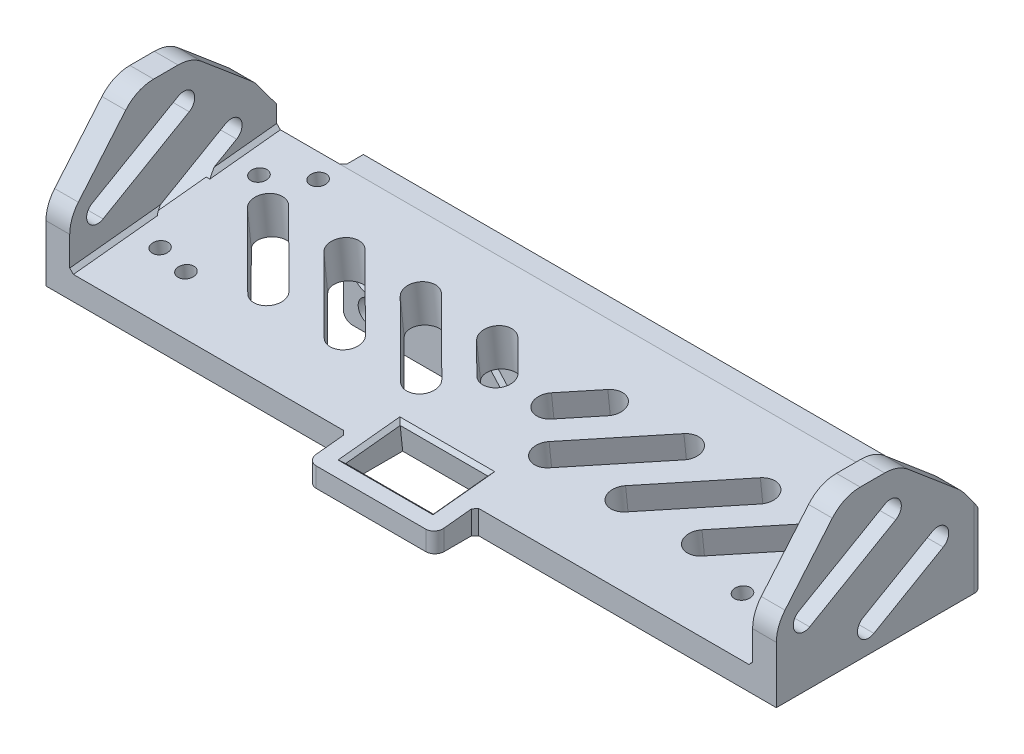
SolidWorks part; units mm, degrees
material "PPS"
ref_plane "前视基准面" through (0, 0, 0) normal (0, 0, 1) x (1, 0, 0)
ref_plane "上视基准面" through (0, 0, 0) normal (0, 1, 0) x (1, 0, 0)
ref_plane "右视基准面" through (0, 0, 0) normal (1, 0, 0) x (0, 0, -1)
sketch "ref" plane through (0, 0, 0) normal (0, 0, 1) x (1, 0, 0)
  line L257 (0, -1000) -> (0, 49000) construction
  line L346 (0, 0) -> (635.1265, 0) construction
  line L351 (-46.1708, 93.9243) -> (-46.1708, 145) construction
  line L358 (-27.9426, 92.9426) -> (-32.5, 97.5) construction
  line L394 (-24.4478, 142.8678) -> (-29.0158, 138.8343)
  line L411 (-32.3253, 137.5823) -> (-39.0335, 137.5823)
  line L414 (-42.3429, 136.3303) -> (-44.4803, 134.4431)
  line L445 (-46.1708, 130.695) -> (-46.1708, 101.1668)
  line L472 (42.3429, 136.3303) -> (44.4803, 134.4431)
  line L494 (46.1729, 155.4291) -> (33.7932, 145.5483) construction
  line L496 (32.4724, 137.5823) -> (39.0335, 137.5823)
  line L497 (25.2455, 142.6568) -> (28.9763, 139.0078)
  line L498 (27.9426, 92.9426) -> (32.5, 97.5) construction
  line L501 (-46.2756, 154.6927) -> (-33.8959, 144.8119) construction
  line L595 (-39.3354, 129.0823) -> (-39.3354, 104.0823) construction
  line L626 (-31.6538, 83.28) -> (-46.1708, 93.9243) construction
  line L628 (-39.3354, 116.5823) -> (0, 116.5823) construction
  line L629 (-15.0322, 144.0823) -> (-9.5322, 138.5823)
  line L630 (-9.5322, 138.5823) -> (9.5322, 138.5823)
  line L631 (15.0322, 144.0823) -> (9.5322, 138.5823)
  line L633 (-21.7494, 144.0823) -> (-15.0322, 144.0823)
  line L635 (15.0322, 144.0823) -> (21.7494, 144.0823)
  line L641 (-9.5322, 83.7633) -> (9.5322, 83.7633)
  line L643 (-9.5322, 83.7633) -> (-14.5322, 78.7633)
  line L644 (30.4418, 78.7633) -> (14.5322, 78.7633) construction
  line L645 (9.5322, 83.7633) -> (14.5322, 78.7633)
  line L646 (7.1054, 96.1323) -> (-7.1054, 96.1323)
  line L647 (-7.1054, 96.1323) -> (-9.7615, 92.339)
  line L648 (-9.7615, 92.339) -> (-9.7615, 90.339)
  line L649 (-9.7615, 90.339) -> (9.7615, 90.339)
  line L652 (9.7615, 92.339) -> (9.7615, 90.339)
  line L653 (7.1054, 96.1323) -> (9.7615, 92.339)
  line L666 (-35.6, 116.5823) -> (-35.6, 112.0823)
  line L668 (-32.5, 116.5823) -> (-32.5, 112.0823)
  line L670 (35.6, 116.5823) -> (35.6, 112.0823)
  line L671 (32.5, 116.5823) -> (32.5, 112.0823)
  line L681 (-19.6882, 78.7633) -> (-14.5322, 78.7633)
  line L686 (14.5322, 78.7633) -> (19.6882, 78.7633)
  line L687 (-42.4964, 96.1323) -> (-35.6, 93.9243)
  line L688 (-35.6, 93.9243) -> (-30.0524, 90.888)
  line L691 (-30.0524, 90.888) -> (-30.0524, 87.8422)
  line L692 (-30.0524, 87.8422) -> (-19.6882, 78.7633)
  line L693 (30.0524, 87.8422) -> (19.6882, 78.7633)
  line L694 (30.0524, 90.888) -> (30.0524, 87.8422)
  line L695 (35.6, 93.9243) -> (30.0524, 90.888)
  line L696 (42.4964, 96.1323) -> (35.6, 93.9243)
  line L697 (46.1708, 130.695) -> (46.1708, 101.1668)
  line L700 (-17.1276, 113.853) -> (-11.5061, 107.6186)
  line L701 (-11.5061, 107.6186) -> (11.5061, 107.6186)
  line L706 (17.1276, 113.853) -> (11.5061, 107.6186)
  line L709 (-7.1054, 129.7982) -> (7.1054, 129.7982)
  line L710 (7.1054, 129.7982) -> (9.7615, 133.5915)
  line L711 (9.7615, 133.5915) -> (9.7615, 135.5915)
  line L712 (9.7615, 135.5915) -> (-9.7615, 135.5915)
  line L713 (-9.7615, 133.5915) -> (-9.7615, 135.5915)
  line L714 (-7.1054, 129.7982) -> (-9.7615, 133.5915)
  line L715 (-24.5927, 117.0678) -> (26.26, 117.0678) construction
  line L717 (17.1276, 113.853) -> (17.1276, 120.2826)
  line L719 (-17.1276, 113.853) -> (-17.1276, 120.2826)
  line L720 (17.1276, 120.2826) -> (11.5061, 126.517)
  line L721 (-17.1276, 120.2826) -> (-11.5061, 126.517)
  line L722 (-11.5061, 126.517) -> (11.5061, 126.517)
  line L723 (-24.5927, 127.9437) -> (-24.5927, 106.192) construction
  line L724 (-22.2052, 127.9437) -> (-22.2052, 106.192)
  line L725 (-26.9801, 127.9437) -> (-26.9801, 106.192)
  line L726 (24.5927, 127.9437) -> (24.5927, 106.192) construction
  line L727 (22.2052, 127.9437) -> (22.2052, 106.192)
  line L728 (26.9801, 127.9437) -> (26.9801, 106.192)
  circle A384 centre (39.3354, 129.0823) radius 2.75
  circle A385 centre (39.3354, 104.0823) radius 2.75
  circle A390 centre (17.238, 84.7633) radius 2.75
  circle A420 centre (-17.238, 84.7633) radius 2.75
  circle A421 centre (-39.3354, 104.0823) radius 2.75
  circle A422 centre (-39.3354, 129.0823) radius 2.75
  arc A453 (32.7926, 143.0294) -> (32.5, 97.5) centre (-120.6696, 121.25) cw construction
  arc A454 (-32.8936, 142.3057) -> (-32.5, 97.5) centre (120.6696, 121.25) ccw construction
  arc A455 (-27.9426, 92.9426) -> (27.9426, 92.9426) centre (0, 290.981) ccw construction
  arc A456 (33.7932, 145.5483) -> (32.7926, 143.0294) centre (35.4973, 143.4132) ccw construction
  arc A457 (-32.8936, 142.3057) -> (-33.8959, 144.8119) centre (-35.6, 142.6768) ccw construction
  arc A473 (-44.4803, 134.4431) -> (-46.1708, 130.695) centre (-41.1708, 130.695) ccw
  arc A474 (-39.0335, 137.5823) -> (-42.3429, 136.3303) centre (-39.0335, 132.5823) ccw
  arc A475 (46.1708, 130.695) -> (44.4803, 134.4431) centre (41.1708, 130.695) ccw
  arc A476 (42.3429, 136.3303) -> (39.0335, 137.5823) centre (39.0335, 132.5823) ccw
  arc A477 (32.4724, 137.5823) -> (28.9763, 139.0078) centre (32.4724, 142.5823) cw
  arc A478 (-29.0158, 138.8343) -> (-32.3253, 137.5823) centre (-32.3253, 142.5823) cw
  arc A479 (25.2455, 142.6568) -> (21.7494, 144.0823) centre (21.7494, 139.0823) ccw
  arc A480 (-21.7494, 144.0823) -> (-24.4478, 142.8678) centre (-21.1384, 139.1198) ccw
  arc A481 (-35.6, 116.5823) -> (-32.5, 116.5823) centre (-34.05, 116.5823) cw
  arc A484 (-35.6, 112.0823) -> (-32.5, 112.0823) centre (-34.05, 112.0823) ccw
  arc A486 (35.6, 116.5823) -> (32.5, 116.5823) centre (34.05, 116.5823) ccw
  arc A487 (35.6, 112.0823) -> (32.5, 112.0823) centre (34.05, 112.0823) cw
  arc A490 (-46.1708, 101.1668) -> (-42.4964, 96.1323) centre (-40.8846, 101.1668) ccw
  arc A491 (46.1708, 101.1668) -> (42.4964, 96.1323) centre (40.8846, 101.1668) cw
  circle A492 centre (17.25, 134.3178) radius 2.75
  circle A493 centre (17.25, 99.8178) radius 2.75
  circle A494 centre (-17.25, 99.8178) radius 2.75
  circle A495 centre (-17.25, 134.3178) radius 2.75
  arc A496 (-22.2052, 127.9437) -> (-26.9801, 127.9437) centre (-24.5927, 127.9437) ccw
  arc A497 (-26.9801, 106.192) -> (-22.2052, 106.192) centre (-24.5927, 106.192) ccw
  arc A498 (22.2052, 127.9437) -> (26.9801, 127.9437) centre (24.5927, 127.9437) cw
  arc A499 (26.9801, 106.192) -> (22.2052, 106.192) centre (24.5927, 106.192) cw
  point P15 (0, 78.5133)
  point P20 (-24.5927, 117.0678)
  point P46 (-46.1708, 132.9503)
  point P50 (-40.925, 137.5823)
  point P53 (46.1708, 132.9503)
  point P56 (40.925, 137.5823)
  point P59 (30.4337, 137.5823)
  point P62 (-30.4337, 137.5823)
  point P65 (23.8205, 144.5823)
  point P69 (-23.8205, 144.5823)
  point P76 (0, 138.5823)
  point P90 (0, 90.339)
  point P92 (0, 96.1323)
  point P118 (0.085, 119.8323)
  point P121 (0, 107.6186)
  point P123 (24.5927, 117.0678)
  point P133 (0, 135.5915)
  point P136 (0, 129.7982)
  point P144 (17.1276, 117.0678)
  point P151 (-17.1276, 117.0678)
  dimension "D1" = 84.7633
  dimension "D2" = 17.238
  dimension "D5" = 44.319
  dimension "D6" = 19.319
  dimension "D7" = 22.0974
  dimension "D8" = 22.0974
  dimension "D9" = 6.5
  dimension "D11" = 46.1708
  dimension "D15" = 33.5
  dimension "D17" = 6
  dimension "D38" = 5.5
  dimension "D39" = 155
  dimension "D40" = 200
  dimension "D27" = 135
  dimension "D31" = 1.55
  dimension "D18" = 34.5
  dimension "D10" = 138.556
  dimension "D12" = 31.6538
  dimension "D13" = 93.9243
  dimension "D14" = 83.28
  dimension "D16" = 5.5
  dimension "D19" = 34.5
  dimension "D25" = 5
  dimension "D26" = 135
  dimension "D28" = 125
  dimension "D29" = 2
  dimension "D30" = 20.45
  dimension "D32" = 32.5
  dimension "D33" = 4.5
sketch "底座" plane through (0, 0, 0) normal (0, 0, 1) x (1, 0, 0)
  line L0 (-37.6416, 127.5678) -> (37.6416, 127.5678)
  line L3 (0, 0) -> (0, 218.6335) construction
  line L4 (0, -201000) -> (0, 249000) construction
  line L5 (-37.6416, 127.5678) -> (-37.6416, 109.336)
  line L8 (-37.6416, 109.336) -> (-17.4308, 109.336)
  line L9 (-17.4308, 109.336) -> (-12.5008, 103.8686)
  line L10 (-12.5008, 103.8686) -> (12.5008, 103.8686)
  line L11 (17.4308, 109.336) -> (12.5008, 103.8686)
  line L12 (37.6416, 109.336) -> (17.4308, 109.336)
  line L13 (37.6416, 127.5678) -> (37.6416, 109.336)
  line L14 (-17.1276, 117.0678) -> (17.1276, 117.0678)
  line L15 (-17.1276, 113.853) -> (-17.1276, 120.2826) construction
  line L16 (17.1276, 117.0678) -> (17.1276, 113.853)
  line L17 (17.1276, 113.853) -> (11.5061, 107.6186)
  line L18 (11.5061, 107.6186) -> (-11.5061, 107.6186)
  line L19 (-11.5061, 107.6186) -> (-17.1276, 113.853)
  line L20 (-17.1276, 113.853) -> (-17.1276, 117.0678)
  circle A5 centre (-34.05, 116.5823) radius 1.55
  circle A6 centre (-34.05, 112.0823) radius 1.55
  circle A7 centre (34.05, 116.5823) radius 1.55
  circle A8 centre (34.05, 112.0823) radius 1.55
  point P22 (0, 103.8686)
  point P33 (0, 127.5678)
  dimension "D1" = 10.5
  dimension "D2" = 3.75
  dimension "D3" = 3.25
extrude "相机底座" add sketch "底座" along normal blind 2.75
sketch "相机支座" plane through (0, 0, 0) normal (1, 0, 0) x (0, 0, -1)
  line L4 (-2.75, 127.5678) -> (-57.8263, 127.5678) construction
  line L6 (-2.75, 127.5678) -> (-31.0939, 124.5888)
  line L7 (-31.0939, 124.5888) -> (-31.0939, 121.3388)
  line L8 (-31.0939, 121.3388) -> (-2.75, 121.3388)
  line L9 (-2.75, 127.5678) -> (-2.75, 109.336) construction
  line L10 (-2.75, 121.3388) -> (-2.75, 127.5678)
  dimension "D1" = 6
  dimension "D2" = 3.25
  dimension "D3" = 28.5
extrude "相机安装座" add sketch "相机支座" along normal blind 50 and the other way blind 50
sketch "USB线槽凸起" plane through (0, 121.3388, 113.8269) normal (0, 1, 0) x (-1, 0, 0)
  line L6 (0, -82.733) -> (0, -111.0769) construction
  line L7 (50, -82.733) -> (-50, -82.733) construction
  line L8 (-37.6416, -111.0769) -> (37.6416, -111.0769) construction
  line L9 (-8.75, -82.733) -> (-8.75, -77.233)
  line L10 (-8.75, -77.233) -> (8.75, -77.233)
  line L11 (8.75, -77.233) -> (8.75, -82.733)
  line L12 (8.75, -82.733) -> (-8.75, -82.733)
  dimension "D2" = 5.5
  dimension "D3" = 17.5
extrude "USB凸起" add sketch "USB线槽凸起" along normal up to surface (3.25 mm away) up to face at (0, 126.5748, 12.198)
sketch "相机减重和螺丝位" plane through (0, 126.4599, 13.2915) normal (0, 0.9945, 0.1045) x (1, 0, 0)
  line L0 (0, -17.9005) -> (0, 10.5995) construction
  line L1 (7.5719, 1.5628) -> (3.7006, -2.3085) construction
  line L5 (37.6416, 10.5995) -> (-37.6416, 10.5995) construction
  line L6 (-8.75, -17.9005) -> (8.75, -17.9005) construction
  line L7 (-6, -13.4308) -> (6, -13.4308)
  line L8 (6, -13.4308) -> (6, -20.9308)
  line L9 (6, -20.9308) -> (-6, -20.9308)
  line L10 (-6, -20.9308) -> (-6, -13.4308)
  line L12 (-8.75, -23.4308) -> (8.75, -23.4308) construction
  line L13 (28.4768, 1.5406) -> (19.2238, -7.7123) construction
  line L14 (29.891, 0.1264) -> (20.638, -9.1266)
  line L15 (27.0626, 2.9549) -> (17.8096, -6.2981)
  line L16 (18.0134, 1.5406) -> (8.7604, -7.7123) construction
  line L17 (19.4276, 0.1264) -> (10.1746, -9.1266)
  line L18 (16.5992, 2.9549) -> (7.3462, -6.2981)
  line L19 (28.4768, 1.5406) -> (18.0134, 1.5406) construction
  line L20 (38.9401, 1.5406) -> (29.6872, -7.7123) construction
  line L21 (40.3543, 0.1264) -> (31.1014, -9.1266)
  line L22 (37.5259, 2.9549) -> (28.2729, -6.2981)
  line L23 (38.9401, 1.5406) -> (28.4768, 1.5406) construction
  line L24 (-38.9401, 1.5406) -> (-29.6872, -7.7123) construction
  line L25 (-40.3543, 0.1264) -> (-31.1014, -9.1266)
  line L26 (-37.5259, 2.9549) -> (-28.2729, -6.2981)
  line L27 (-28.4768, 1.5406) -> (-19.2238, -7.7123) construction
  line L28 (-29.891, 0.1264) -> (-20.638, -9.1266)
  line L29 (-27.0626, 2.9549) -> (-17.8096, -6.2981)
  line L30 (-18.0134, 1.5406) -> (-8.7604, -7.7123) construction
  line L31 (-19.4276, 0.1264) -> (-10.1746, -9.1266)
  line L32 (-16.5992, 2.9549) -> (-7.3462, -6.2981)
  line L43 (8.9861, 0.1486) -> (5.1148, -3.7227)
  line L46 (6.1576, 2.977) -> (2.2863, -0.8943)
  line L47 (18.0352, 1.5628) -> (7.5719, 1.5628) construction
  line L48 (-7.5719, 1.5628) -> (-3.7006, -2.3085) construction
  line L49 (-8.9861, 0.1486) -> (-5.1148, -3.7227)
  line L50 (-6.1576, 2.977) -> (-2.2863, -0.8943)
  circle A0 centre (38.1, -10.6005) radius 1.1
  circle A1 centre (-38.1, -10.6005) radius 1.1
  circle A2 centre (38.1, 7.5995) radius 1.1
  circle A3 centre (-38.1, 7.5995) radius 1.1
  arc A4 (29.891, 0.1264) -> (27.0626, 2.9549) centre (28.4768, 1.5406) ccw
  arc A5 (17.8096, -6.2981) -> (20.638, -9.1266) centre (19.2238, -7.7123) ccw
  arc A6 (19.4276, 0.1264) -> (16.5992, 2.9549) centre (18.0134, 1.5406) ccw
  arc A7 (7.3462, -6.2981) -> (10.1746, -9.1266) centre (8.7604, -7.7123) ccw
  arc A8 (40.3543, 0.1264) -> (37.5259, 2.9549) centre (38.9401, 1.5406) ccw
  arc A9 (28.2729, -6.2981) -> (31.1014, -9.1266) centre (29.6872, -7.7123) ccw
  arc A10 (-40.3543, 0.1264) -> (-37.5259, 2.9549) centre (-38.9401, 1.5406) cw
  arc A11 (-28.2729, -6.2981) -> (-31.1014, -9.1266) centre (-29.6872, -7.7123) cw
  arc A12 (-29.891, 0.1264) -> (-27.0626, 2.9549) centre (-28.4768, 1.5406) cw
  arc A13 (-17.8096, -6.2981) -> (-20.638, -9.1266) centre (-19.2238, -7.7123) cw
  arc A14 (-19.4276, 0.1264) -> (-16.5992, 2.9549) centre (-18.0134, 1.5406) cw
  arc A15 (-7.3462, -6.2981) -> (-10.1746, -9.1266) centre (-8.7604, -7.7123) cw
  circle A16 centre (-43, 4.3792) radius 1.1
  circle A17 centre (-42.615, -9.6155) radius 1.0865
  circle A18 centre (43, 4.3792) radius 1.1
  circle A19 centre (42.615, -9.6155) radius 1.0865
  arc A36 (8.9861, 0.1486) -> (6.1576, 2.977) centre (7.5719, 1.5628) ccw
  arc A37 (2.2863, -0.8943) -> (5.1148, -3.7227) centre (3.7006, -2.3085) ccw
  arc A38 (-8.9861, 0.1486) -> (-6.1576, 2.977) centre (-7.5719, 1.5628) cw
  arc A39 (-2.2863, -0.8943) -> (-5.1148, -3.7227) centre (-3.7006, -2.3085) cw
  point P24 (23.8503, -3.0858)
  point P29 (13.3869, -3.0858)
  point P41 (34.3136, -3.0858)
  point P48 (3.7394, -2.3904)
  point P51 (-34.3136, -3.0858)
  point P58 (-23.8503, -3.0858)
  point P65 (-13.3869, -3.0858)
  point P77 (5.6362, -0.3728)
  point P87 (-5.6362, -0.3728)
  dimension "D4" = 2.2
  dimension "D1" = 18.2
  dimension "D2" = 3
  dimension "D3" = 76.2
  dimension "D5" = 7.5
  dimension "D6" = 2.5
  dimension "D7" = 12
  dimension "D8" = 45
  dimension "D9" = 4
  dimension "D10" = 86
  dimension "D11" = 14
extrude "相机面细节" cut sketch "相机减重和螺丝位" against normal up to surface (2.9494 mm away) up to face at (0, 121.3388, 20.8563)
sketch "结构支撑" plane through (0, 0, 0) normal (1, 0, 0) x (0, 0, -1)
  line L0 (-6.4122, 121.3388) -> (-2.75, 121.3388)
  line L1 (-31.0939, 121.3388) -> (-2.75, 121.3388) construction
  line L2 (-2.75, 121.3388) -> (-2.75, 119.5442)
  line L3 (-2.75, 109.336) -> (-2.75, 121.3388) construction
  line L4 (-2.75, 119.5442) -> (-6.4122, 121.3388)
extrude "相机面结构补强-1" add sketch "结构支撑" along normal blind 5 from offset 15
extrude "相机面结构补强-2" add sketch "结构支撑<2>" against normal blind 5 from offset 15 offset against normal yes
sketch "结构支撑<2>" plane through (0, 0, 0) normal (1, 0, 0) x (0, 0, -1) same geometry as "结构支撑"
sketch "相机保护" plane through (50, 0, 0) normal (1, 0, 0) x (0, 0, -1)
  line L0 (-31.0939, 121.3388) -> (-31.0939, 130.9161)
  line L1 (-31.0939, 130.9161) -> (-21.9356, 141.7607)
  line L2 (-21.9356, 141.7607) -> (-14.4356, 141.7607)
  line L3 (-14.4356, 141.7607) -> (-5.7426, 134.4195)
  line L5 (-2.75, 121.3388) -> (-31.0939, 121.3388)
  line L6 (-5.7426, 134.4195) -> (-2.75, 130.3511)
  line L7 (-2.75, 130.3511) -> (-2.75, 121.3388)
  line L8 (-15.4869, 136.7485) -> (-27.2814, 129.939) construction
  line L9 (-14.7369, 135.4495) -> (-26.5314, 128.6399)
  line L10 (-16.2369, 138.0476) -> (-28.0314, 131.238)
  line L11 (-15.4869, 136.7485) -> (-8.9956, 130.2573) construction
  line L15 (-8.9956, 130.2573) -> (-18.4848, 124.7787) construction
  line L16 (-8.2456, 128.9582) -> (-17.7348, 123.4796)
  line L17 (-9.7456, 131.5563) -> (-19.2348, 126.0777)
  arc A0 (-14.7369, 135.4495) -> (-16.2369, 138.0476) centre (-15.4869, 136.7485) ccw
  arc A1 (-28.0314, 131.238) -> (-26.5314, 128.6399) centre (-27.2814, 129.939) ccw
  arc A4 (-8.2456, 128.9582) -> (-9.7456, 131.5563) centre (-8.9956, 130.2573) ccw
  arc A5 (-19.2348, 126.0777) -> (-17.7348, 123.4796) centre (-18.4848, 124.7787) ccw
  point P3 (-21.3841, 133.3438)
  point P27 (-13.7402, 127.518)
  line M8 (-2.75, 127.5678) -> (-31.0939, 124.5888)
  dimension "D4" = 1.5
  dimension "D1" = 17.75
  dimension "D2" = 7.5
  dimension "D3" = 60
  dimension "D5" = 45
extrude "相机保护-右" add sketch "相机保护" against normal blind 3.25
extrude "相机保护-左" add sketch "相机保护<2>" along normal blind 3.25 from surface starting at face at (-50, 123.7085, 16.9219)
sketch "相机保护<2>" plane through (50, 0, 0) normal (1, 0, 0) x (0, 0, -1) same geometry as "相机保护"
extrude "美观-1" cut sketch "相机保护<3>" against normal blind 3.25 from surface contours L17 A5 L16 A4 M8 | A5 L16 M8 region at (50, 125.0424, 17.1808) region at (50, 128.5657, 12.284) starting at face at (50, 127.9412, 13.5871)
sketch "相机保护<3>" plane through (50, 0, 0) normal (1, 0, 0) x (0, 0, -1) same geometry as "相机保护"
extrude "美观-2" cut sketch "相机保护<4>" along normal blind 3.25 from surface contours A5 L16 M8 | L17 A5 L16 A4 M8 region at (50, 125.0424, 17.1808) region at (50, 128.5657, 12.284) starting at face at (-50, 127.9412, 13.5871)
sketch "相机保护<4>" plane through (50, 0, 0) normal (1, 0, 0) x (0, 0, -1) same geometry as "相机保护"
chamfer "倒角1" distance 0.5 angle 45 18 edges at (17.1276, 115.4604, 2.75) (14.3168, 110.7358, 2.75) (0, 107.6186, 2.75) (-14.3168, 110.7358, 2.75) (-17.1276, 115.4604, 2.75) (0, 117.0678, 2.75) (0, 125.056, 26.6487) (6, 124.664, 30.3781) (0, 124.272, 34.1076) (-6, 124.664, 30.3781) (8.75, 122.9638, 31.0939) (-8.75, 122.9638, 31.0939) (-46.75, 127.06, 7.5815) (-46.75, 125.1936, 25.3394) (46.75, 127.06, 7.5815) (46.75, 125.1936, 25.3394) (37.6416, 124.4533, 2.75) (-37.6416, 124.4533, 2.75)
chamfer "倒角2" distance 1 angle 45 2 edges at (35.6, 116.5823, 2.75) (-32.5, 116.5823, 2.75)
fillet "圆角1" radius 1.25 6 edges at (-8.75, 122.6747, 36.5939) (8.75, 122.6747, 36.5939) (-50, 125.8449, 2.75) (50, 125.8449, 2.75) (-37.6416, 109.336, 1.375) (37.6416, 109.336, 1.375)
fillet "圆角2" radius 5 12 edges at (-17.4308, 109.336, 1.375) (-12.5008, 103.8686, 1.375) (12.5008, 103.8686, 1.375) (17.4308, 109.336, 1.375) (-48.375, 134.4195, 5.7426) (-48.375, 141.7607, 14.4356) (-48.375, 141.7607, 21.9356) (48.375, 134.4195, 5.7426) (48.375, 141.7607, 14.4356) (48.375, 141.7607, 21.9356) (48.375, 130.9161, 31.0939) (-48.375, 130.9161, 31.0939)
sketch "螺母位" plane through (0, 127.8211, 0.3397) normal (0, -0.9945, -0.1045) x (1, 0, 0)
  line L25 (36.6566, 21.1235) -> (39.5434, 21.1235)
  line L26 (39.5434, 21.1235) -> (40.9868, 23.6235)
  line L27 (40.9868, 23.6235) -> (39.5434, 26.1235)
  line L28 (39.5434, 26.1235) -> (36.6566, 26.1235)
  line L29 (36.6566, 26.1235) -> (35.2132, 23.6235)
  line L30 (35.2132, 23.6235) -> (36.6566, 21.1235)
  line L31 (36.6566, 2.9235) -> (39.5434, 2.9235)
  line L32 (39.5434, 2.9235) -> (40.9868, 5.4235)
  line L33 (40.9868, 5.4235) -> (39.5434, 7.9235)
  line L34 (39.5434, 7.9235) -> (36.6566, 7.9235)
  line L35 (36.6566, 7.9235) -> (35.2132, 5.4235)
  line L36 (35.2132, 5.4235) -> (36.6566, 2.9235)
  line L37 (-40.9868, 23.6235) -> (-39.5434, 21.1235)
  line L38 (-39.5434, 21.1235) -> (-36.6566, 21.1235)
  line L39 (-36.6566, 21.1235) -> (-35.2132, 23.6235)
  line L40 (-35.2132, 23.6235) -> (-36.6566, 26.1235)
  line L41 (-36.6566, 26.1235) -> (-39.5434, 26.1235)
  line L42 (-39.5434, 26.1235) -> (-40.9868, 23.6235)
  line L43 (-39.5434, 2.9235) -> (-36.6566, 2.9235)
  line L44 (-36.6566, 2.9235) -> (-35.2132, 5.4235)
  line L45 (-35.2132, 5.4235) -> (-36.6566, 7.9235)
  line L46 (-36.6566, 7.9235) -> (-39.5434, 7.9235)
  line L47 (-39.5434, 7.9235) -> (-40.9868, 5.4235)
  line L48 (-40.9868, 5.4235) -> (-39.5434, 2.9235)
  line L55 (-41.1716, 20.1386) -> (-39.7283, 22.6386)
  line L56 (-39.7283, 22.6386) -> (-41.1716, 25.1386)
  line L57 (-41.1716, 25.1386) -> (-44.0584, 25.1386)
  line L58 (-44.0584, 25.1386) -> (-45.5018, 22.6386)
  line L59 (-45.5018, 22.6386) -> (-44.0584, 20.1386)
  line L60 (-44.0584, 20.1386) -> (-41.1716, 20.1386)
  line L61 (-41.5566, 6.1439) -> (-40.1132, 8.6439)
  line L62 (-40.1132, 8.6439) -> (-41.5566, 11.1439)
  line L63 (-41.5566, 11.1439) -> (-44.4434, 11.1439)
  line L64 (-44.4434, 11.1439) -> (-45.8868, 8.6439)
  line L65 (-45.8868, 8.6439) -> (-44.4434, 6.1439)
  line L66 (-44.4434, 6.1439) -> (-41.5566, 6.1439)
  line L67 (44.4434, 6.1439) -> (45.8868, 8.6439)
  line L68 (45.8868, 8.6439) -> (44.4434, 11.1439)
  line L69 (44.4434, 11.1439) -> (41.5566, 11.1439)
  line L70 (41.5566, 11.1439) -> (40.1132, 8.6439)
  line L71 (40.1132, 8.6439) -> (41.5566, 6.1439)
  line L72 (41.5566, 6.1439) -> (44.4434, 6.1439)
  line L73 (44.0584, 20.1386) -> (45.5018, 22.6386)
  line L74 (45.5018, 22.6386) -> (44.0584, 25.1386)
  line L75 (44.0584, 25.1386) -> (41.1716, 25.1386)
  line L76 (41.1716, 25.1386) -> (39.7283, 22.6386)
  line L77 (39.7283, 22.6386) -> (41.1716, 20.1386)
  line L78 (41.1716, 20.1386) -> (44.0584, 20.1386)
  circle A0 centre (38.1, 23.6235) radius 2.5 construction
  circle A1 centre (38.1, 23.6235) radius 1.1 construction
  circle A2 centre (38.1, 5.4235) radius 2.5 construction
  circle A3 centre (38.1, 5.4235) radius 1.1 construction
  circle A4 centre (-38.1, 5.4235) radius 1.1 construction
  circle A5 centre (-38.1, 23.6235) radius 2.5 construction
  circle A6 centre (-38.1, 5.4235) radius 2.5 construction
  circle A7 centre (-38.1, 23.6235) radius 1.1 construction
  circle A8 centre (-42.615, 22.6386) radius 2.5 construction
  circle A11 centre (-43, 8.6439) radius 2.5 construction
  circle A12 centre (43, 8.6439) radius 2.5 construction
  circle A13 centre (42.615, 22.6386) radius 2.5 construction
  circle A14 centre (42.615, 22.6386) radius 1.0865 construction
  circle A15 centre (43, 8.6439) radius 1.1 construction
  circle A16 centre (-43, 8.6439) radius 1.1 construction
  circle A17 centre (-42.615, 22.6386) radius 1.0865 construction
  dimension "D1" = 5
extrude "螺母" cut sketch "螺母位" against normal blind 1.25 and the other way blind 4 from offset 4.5 contours L60 L59 L58 L57 L56 L42 L37 L55 | L55 L56 L42 L41 L40 L39 L38 L37 | L66 L65 L64 L63 L62 L61 | L48 L47 L46 L45 L44 L43 | L76 L77 L26 L25 L30 L29 L28 L27 | L78 L77 L26 L27 L76 L75 L74 L73 | L72 L71 L70 L69 L68 L67 | L36 L35 L34 L33 L32 L31 | L77 L76 L27 L26 | L56 L55 L37 L42 region at (37.9801, 125.3491, 23.8599) region at (40.3575, 125.4033, 23.3441) region at (42.7349, 125.4575, 22.8283) region at (38.1, 127.2542, 5.7336) region at (-40.3575, 125.4033, 23.3441) region at (-42.7349, 125.4575, 22.8283) region at (-37.9801, 125.3491, 23.8599) region at (-38.1, 127.2542, 5.7336) region at (-43, 126.9176, 8.9363) region at (43, 126.9176, 8.9363)
